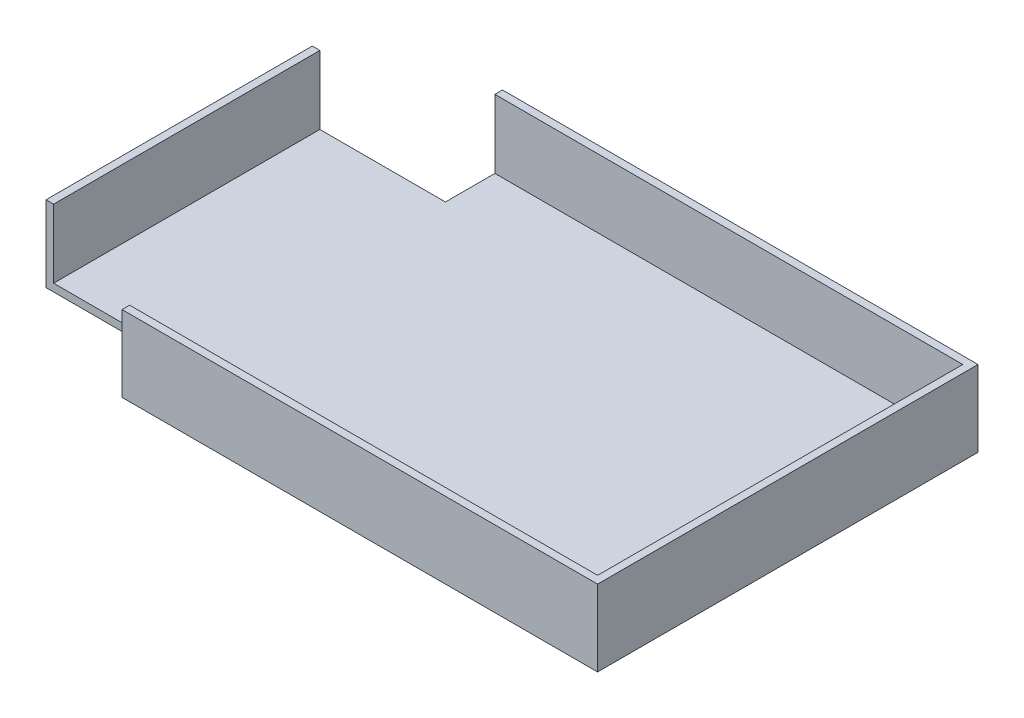
SolidWorks part; units mm, degrees
ref_plane "Front Plane" through (0, 0, 0) normal (0, 0, 1) x (1, 0, 0)
ref_plane "Top Plane" through (0, 0, 0) normal (0, 1, 0) x (1, 0, 0)
ref_plane "Right Plane" through (0, 0, 0) normal (1, 0, 0) x (0, 0, -1)
sketch "Sketch1" plane through (0, 0, 0) normal (0, 1, 0) x (1, 0, 0)
  line L0 (-101.6, 44.45) -> (-57.15, 44.45)
  line L1 (-57.15, 63.5) -> (101.6, 63.5)
  line L2 (-101.6, 44.45) -> (-101.6, -44.45)
  line L3 (-57.15, -63.5) -> (101.6, -63.5)
  line L4 (101.6, 63.5) -> (101.6, -63.5)
  line L9 (-57.15, 44.45) -> (-57.15, 63.5)
  line L10 (-101.6, -44.45) -> (-57.15, -44.45)
  line L11 (-57.15, -44.45) -> (-57.15, -63.5)
  point P6 (101.6, 0)
  dimension "D2" = 127
  dimension "D3" = 203.2
  dimension "D6" = 19.05
  dimension "D7" = 44.45
extrude "Boss-Extrude1" add sketch "Sketch1" along normal blind 25.4
sketch "Sketch2" plane through (0, 25.4, 0) normal (0, 1, 0) x (1, 0, 0)
  line L0 (101.6, 63.5) -> (-57.15, 63.5) construction
  line L1 (-99.06, 60.96) -> (99.06, 60.96)
  line L2 (-99.06, 60.96) -> (-99.06, -60.96)
  line L3 (-99.06, -60.96) -> (99.06, -60.96)
  line L4 (99.06, 60.96) -> (99.06, -60.96)
  line L5 (101.6, -63.5) -> (101.6, 63.5) construction
  point P8 (0, 60.96)
  point P11 (99.06, 0)
  dimension "D1" = 2.54
  dimension "D2" = 2.54
extrude "Cut-Extrude1" cut sketch "Sketch2" against normal blind 22.86
sketch "Sketch4" plane through (0, 2.54, 0) normal (0, 1, 0) x (1, 0, 0)
  line L0 (99.06, 60.96) -> (-57.15, 60.96) construction
  line L1 (-27.94, 60.96) -> (-25.4, 60.96)
  line L2 (-27.94, 60.96) -> (-27.94, -60.96)
  line L3 (-27.94, -60.96) -> (-25.4, -60.96)
  line L4 (-25.4, 60.96) -> (-25.4, -60.96)
  line L6 (-57.15, -60.96) -> (99.06, -60.96) construction
  dimension "D1" = 2.54
sketch "Sketch3" plane through (0, 25.4, 0) normal (0, 1, 0) x (1, 0, 0)
  line L0 (101.6, -63.5) -> (101.6, 63.5) construction
  line L1 (99.06, 60.96) -> (101.6, 60.96)
  line L2 (99.06, 60.96) -> (99.06, -60.96)
  line L3 (99.06, -60.96) -> (101.6, -60.96)
  line L4 (101.6, 60.96) -> (101.6, -60.96)
  line L5 (99.06, -60.96) -> (-57.15, -60.96) construction
sketch "Sketch5" plane through (0, 0, 0) normal (0, 0, 1) x (1, 0, 0)
  line L4 (-27.94, 2.54) -> (55.5767, 2.54) construction
  line L5 (55.5767, 2.54) -> (101.6, 25.4) construction
  spline S0 degree 2 poles (-27.94, 2.54) (55.5767, 2.54) (101.6, 25.4) knots 0 0 0 1 1 1
